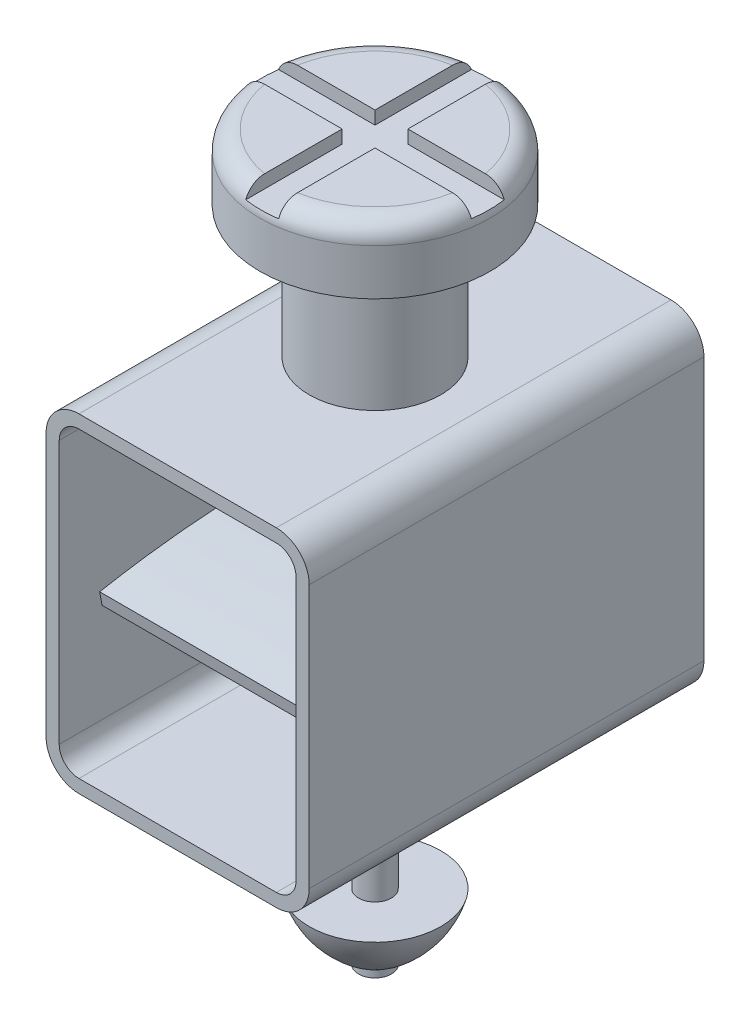
SolidWorks part; units mm, degrees
ref_plane "Ön Düzlem" through (0, 0, 0) normal (0, 0, 1) x (1, 0, 0)
ref_plane "Üst Düzlem" through (0, 0, 0) normal (0, 1, 0) x (1, 0, 0)
ref_plane "Sağ Düzlem" through (0, 0, 0) normal (1, 0, 0) x (0, 0, -1)
sketch "Çizim1" plane through (0, 0, 0) normal (0, 0, 1) x (1, 0, 0)
  line L0 (-1.8, 2) -> (-1.8, -2)
  line L1 (-1.5, 2.5) -> (1.5, 2.5)
  line L2 (-2, 2) -> (-2, -2)
  line L3 (-1.5, -2.5) -> (1.5, -2.5)
  line L4 (2, 2) -> (2, -2)
  line L5 (-2, 2.5) -> (2, -2.5) construction
  line L6 (-2, -2.5) -> (2, 2.5) construction
  line L7 (-1.5, -2.3) -> (1.5, -2.3)
  line L8 (1.8, 2) -> (1.8, -2)
  line L9 (-1.5, 2.3) -> (1.5, 2.3)
  arc A0 (1.5, -2.5) -> (2, -2) centre (1.5, -2) ccw
  arc A1 (-2, -2) -> (-1.5, -2.5) centre (-1.5, -2) ccw
  arc A2 (1.5, 2.5) -> (2, 2) centre (1.5, 2) cw
  arc A3 (-1.5, 2.5) -> (-2, 2) centre (-1.5, 2) ccw
  arc A4 (-1.8, -2) -> (-1.5, -2.3) centre (-1.5, -2) ccw
  arc A5 (1.5, -2.3) -> (1.8, -2) centre (1.5, -2) ccw
  arc A6 (1.5, 2.3) -> (1.8, 2) centre (1.5, 2) cw
  arc A7 (-1.5, 2.3) -> (-1.8, 2) centre (-1.5, 2) ccw
  point P0 (0, 0)
  dimension "D3" = 0.5
  dimension "D1" = 4
  dimension "D2" = 5
  dimension "D4" = 0.2
extrude "Yükseklik-Ekstrüzyon1" add sketch "Çizim1" along normal blind 3 and the other way blind 3
ref_plane "Düzlem1" through (0, 0, 0) normal (1, 0, 0) x (0, 0, -1)
sketch "Çizim10" plane through (0, 0, 0) normal (1, 0, 0) x (0, 0, -1)
  line L0 (-3, 0) -> (3, 0) construction
  line L1 (-3, -2) -> (-3, 2) construction
  line L2 (3, -2) -> (3, 2) construction
  line L3 (-2.6849, 0) -> (-2.6483, -0.1966)
  line L4 (-2.6849, 0.25) -> (2.6849, 0.25) construction
  line L5 (-2.6849, 0.25) -> (-2.6849, -0.25) construction
  line L6 (-2.6849, -0.25) -> (2.6849, -0.25) construction
  line L7 (2.6849, 0.25) -> (2.6849, -0.25) construction
  line L8 (-2.6849, 0.25) -> (2.6849, -0.25) construction
  line L9 (-2.6849, -0.25) -> (2.6849, 0.25) construction
  line L10 (2.6849, 0) -> (2.6483, -0.1966)
  spline S0 degree 3 poles (-2.6849, 0) (-0.895, 0.3333) (0.895, 0.3333) (2.6849, 0) knots 0 0 0 0 1 1 1 1
  spline S1 degree 1 poles (-2.6483, -0.1966) (2.6483, -0.1966) knots 0 0 1 1 construction
  spline S2 degree 3 poles (-2.6483, -0.1966) (-0.9126, 0.1266) (0.9126, 0.1266) (2.6483, -0.1966) knots 0 0 0 0 1 1 1 1
  point P6 (0, 0)
  dimension "D1" = 0.5
  dimension "D2" = 0.2
extrude "Yükseklik-Ekstrüzyon7" add sketch "Çizim10" along normal blind 1.5 and the other way blind 1.5 separate body
sketch "Çizim11" plane through (0, 2.5, 0) normal (0, 1, 0) x (1, 0, 0)
  circle A0 centre (0, 0) radius 1
  dimension "D1" = 2
extrude "Yükseklik-Ekstrüzyon8" add sketch "Çizim11" along normal blind 2 and the other way blind 3
fillet "Radyus3" radius 0.3 1 edges at (0, -0.5, 1)
sketch "Çizim12" plane through (0, 4.5, 0) normal (0, 1, 0) x (1, 0, 0)
  circle A0 centre (0, 0) radius 1.75
  dimension "D1" = 3.5
extrude "Yükseklik-Ekstrüzyon9" add sketch "Çizim12" along normal blind 1
fillet "Radyus4" radius 0.3 1 edges at (0, 5.5, 1.75)
sketch "Çizim13" plane through (0, 5.5, 0) normal (0, 1, 0) x (1, 0, 0)
  line L0 (-0.25, -0.25) -> (-0.25, -2.0966)
  line L1 (-0.25, 2.0966) -> (0.25, 2.0966)
  line L2 (-0.25, 2.0966) -> (-0.25, 0.25)
  line L3 (-0.25, -2.0966) -> (0.25, -2.0966)
  line L4 (0.25, 2.0966) -> (0.25, 0.25)
  line L7 (-2.7097, 0.25) -> (-0.25, 0.25)
  line L8 (-2.7097, 0.25) -> (-2.7097, -0.25)
  line L9 (-2.7097, -0.25) -> (-0.25, -0.25)
  line L10 (2.7097, 0.25) -> (2.7097, -0.25)
  line L14 (0.25, 0.25) -> (2.7097, 0.25)
  line L16 (0.25, -0.25) -> (0.25, -2.0966)
  line L18 (0.25, -0.25) -> (2.7097, -0.25)
  point P0 (0, 0)
  point P6 (0, 0)
  dimension "D1" = 0.5
  dimension "D2" = 0.5
extrude "Kes-Ekstrüzyon5" cut sketch "Çizim13" against normal blind 0.2
sketch "Çizim14" plane through (0, -2.5, 0) normal (0, -1, 0) x (1, 0, 0)
  circle A0 centre (0, 0) radius 0.25
  dimension "D1" = 0.5
extrude "Yükseklik-Ekstrüzyon10" add sketch "Çizim14" along normal blind 3
ref_plane "Düzlem3" through (0, 0, 0) normal (1, 0, 0) x (0, 0, -1)
sketch "Çizim15" plane through (0, 0, 0) normal (1, 0, 0) x (0, 0, -1)
  line L0 (0, -5.5) -> (0, -4.5)
  line L1 (-0.25, -5.5) -> (0.25, -5.5) construction
  line L2 (0, -4.5) -> (1, -4.5)
  spline S0 degree 2 poles (0, -5.5) (0.8124, -5.1587) (1, -4.5) knots 0 0 0 0.798476 0.798476 0.798476
  dimension "D1" = 1
  dimension "D2" = 1
revolve "Döndür2" add sketch "Çizim15" angle 360 about L0
